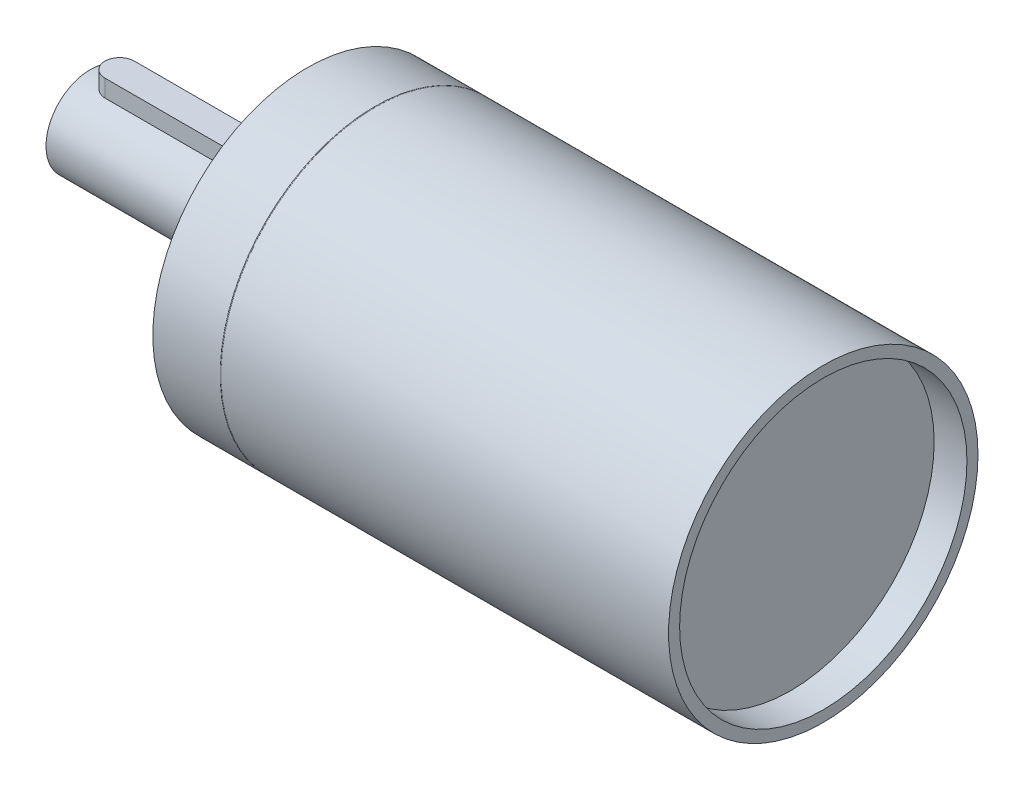
SolidWorks part; units mm, degrees
ref_plane "Front Plane" through (0, 0, 0) normal (0, 0, 1) x (1, 0, 0)
ref_plane "Top Plane" through (0, 0, 0) normal (0, 1, 0) x (1, 0, 0)
ref_plane "Right Plane" through (0, 0, 0) normal (1, 0, 0) x (0, 0, -1)
sketch "Sketch1" plane through (0, 0, 0) normal (0, 0, 1) x (1, 0, 0)
  line L0 (0, 21) -> (0, 0)
  line L1 (0, 0) -> (70, 0)
  line L2 (70, 0) -> (70, 21)
  line L3 (70, 21) -> (9.25, 21)
  line L4 (9.15, 21) -> (0, 21)
  line L5 (0, 0) -> (70, 0) construction
  arc A0 (9.25, 21) -> (9.15, 21) centre (9.2, 21.0866) cw
revolve "Revolve1" add sketch "Sketch1" angle 360 about L5 reverse direction yes
sketch "Sketch2" plane through (0, 0, 0) normal (-1, 0, 0) x (0, 0, 1)
  circle A0 centre (0, 0) radius 14
extrude "Boss-Extrude1" add sketch "Sketch2" along normal blind 3
sketch "Sketch3" plane through (-3, 0, 0) normal (-1, 0, 0) x (0, 0, 1)
  circle A0 centre (0, 0) radius 6
extrude "Boss-Extrude2" add sketch "Sketch3" along normal blind 26.5
sketch "Sketch4" plane through (-3, 0, 0) normal (-1, 0, 0) x (0, 0, 1)
  line L0 (0.2939, -7.6168) -> (0.2939, -5.9928)
  line L1 (-0.2939, -5.9928) -> (-0.2939, -7.6168)
  arc A0 (0.2939, -5.9928) -> (-0.2939, -5.9928) centre (0, 0) ccw
  arc A1 (-0.2939, -7.6168) -> (-2.8825, -5.9928) centre (0.2939, -3.8048) cw
  arc A2 (-2.8825, -5.9928) -> (2.8825, -5.9928) centre (0, 0) cw
  arc A3 (2.8825, -5.9928) -> (0.2939, -7.6168) centre (0.2939, -4.7418) cw
extrude "Boss-Extrude3" add sketch "Sketch4" along normal blind 1
ref_plane "Plane1" through (0, 8, 0) normal (0, 1, 0) x (-1, 0, 0)
sketch "Sketch5" plane through (0, 8, 0) normal (0, 1, 0) x (-1, 0, 0)
  line L0 (9.5, -2) -> (25.5, -2)
  line L1 (25.5, 2) -> (9.5, 2)
  arc A0 (25.5, -2) -> (25.5, 2) centre (25.5, 0) ccw
  arc A1 (9.5, 2) -> (9.5, -2) centre (9.5, 0) ccw
extrude "Boss-Extrude4" add sketch "Sketch5" against normal up to next
hole_wizard "Hole1" positions "Sketch7" profile "Sketch6" legacy
sketch "Sketch7" plane through (70, 0, 0) normal (1, 0, 0) x (0, 0, -1)
  point P0 (0, 0)
sketch "Sketch6" plane through (70, 0, 0) normal (0, 1, 0) x (0, 0, -1)
  line L0 (0, 0) -> (0, 4.45)
  line L1 (0, 4.45) -> (19.5, 4.45)
  line L2 (19.5, 4.45) -> (19.5, 0)
  line L3 (19.5, 0) -> (0, 0)
  line L4 (0, 110) -> (0, -10) construction
  dimension "Diameter" = 39
  dimension "Depth" = 4.45
hole_wizard "Hole2" positions "Sketch9" profile "Sketch8" legacy
sketch "Sketch9" plane through (0, 0, 0) normal (-1, 0, 0) x (0, 0, 1)
  point P0 (-17.5, 0)
sketch "Sketch8" plane through (0, 0, -17.5) normal (0, 1, 0) x (0, 0, 1)
  line L0 (0, 0) -> (0, 6.9914)
  line L1 (0, 6.9914) -> (1.65, 6)
  line L2 (1.65, 6) -> (1.65, 0)
  line L4 (1.65, 0) -> (0, 0)
  line L6 (0, 6.9914) -> (-1.65, 6) construction
  line L7 (0, -4.2442) -> (0, 117.3081) construction
  dimension "Diameter" = 3.3
  dimension "Depth" = 6
  dimension "Drill Angle" = 118
hole_wizard "Hole3" positions "Sketch11" profile "Sketch10" legacy
sketch "Sketch11" plane through (0, 0, 0) normal (-1, 0, 0) x (0, 0, 1)
  point P0 (0, -17.5)
sketch "Sketch10" plane through (0, -17.5, 0) normal (0, 1, 0) x (0, 0, 1)
  line L0 (0, 0) -> (0, 6.9914)
  line L1 (0, 6.9914) -> (1.65, 6)
  line L2 (1.65, 6) -> (1.65, 0)
  line L4 (1.65, 0) -> (0, 0)
  line L6 (0, 6.9914) -> (-1.65, 6) construction
  line L7 (0, -4.2442) -> (0, 117.3081) construction
  dimension "Diameter" = 3.3
  dimension "Depth" = 6
  dimension "Drill Angle" = 118
hole_wizard "Hole4" positions "Sketch13" profile "Sketch12" legacy
sketch "Sketch13" plane through (0, 0, 0) normal (-1, 0, 0) x (0, 0, 1)
  point P0 (17.5, 0)
sketch "Sketch12" plane through (0, 0, 17.5) normal (0, 1, 0) x (0, 0, 1)
  line L0 (0, 0) -> (0, 6.9914)
  line L1 (0, 6.9914) -> (1.65, 6)
  line L2 (1.65, 6) -> (1.65, 0)
  line L4 (1.65, 0) -> (0, 0)
  line L6 (0, 6.9914) -> (-1.65, 6) construction
  line L7 (0, -4.2442) -> (0, 117.3081) construction
  dimension "Diameter" = 3.3
  dimension "Depth" = 6
  dimension "Drill Angle" = 118
hole_wizard "Hole5" positions "Sketch15" profile "Sketch14" legacy
sketch "Sketch15" plane through (0, 0, 0) normal (-1, 0, 0) x (0, 0, 1)
  point P0 (0, 17.5)
sketch "Sketch14" plane through (0, 17.5, 0) normal (0, 1, 0) x (0, 0, 1)
  line L0 (0, 0) -> (0, 6.9914)
  line L1 (0, 6.9914) -> (1.65, 6)
  line L2 (1.65, 6) -> (1.65, 0)
  line L4 (1.65, 0) -> (0, 0)
  line L6 (0, 6.9914) -> (-1.65, 6) construction
  line L7 (0, -4.2442) -> (0, 117.3081) construction
  dimension "Diameter" = 3.3
  dimension "Depth" = 6
  dimension "Drill Angle" = 118
hole_wizard "Hole6" positions "Sketch17" profile "Sketch16" legacy
sketch "Sketch17" plane through (-29.5, 0, 0) normal (-1, 0, 0) x (0, 0, 1)
  point P0 (0, 0)
sketch "Sketch16" plane through (-29.5, 0, 0) normal (0, 1, 0) x (0, 0, 1)
  line L0 (0, 0) -> (0, 2.3)
  line L1 (0, 2.3) -> (0.625, 1.9392)
  line L2 (0.625, 1.9392) -> (0.625, 1.2124)
  line L3 (0.625, 1.2124) -> (1.325, 0)
  line L4 (1.325, 0) -> (0, 0)
  line L5 (0, -14.3089) -> (0, 102.4216) construction
  line L6 (0, 2.3) -> (-0.625, 1.9392) construction
  line L7 (-0.625, 1.2124) -> (-1.325, 0) construction
  dimension "Diameter" = 1.25
  dimension "Depth" = 1.9392
  dimension "C-Sink Diameter" = 2.65
  dimension "C-Sink Angle" = 60
  dimension "Drill Angle" = 120
